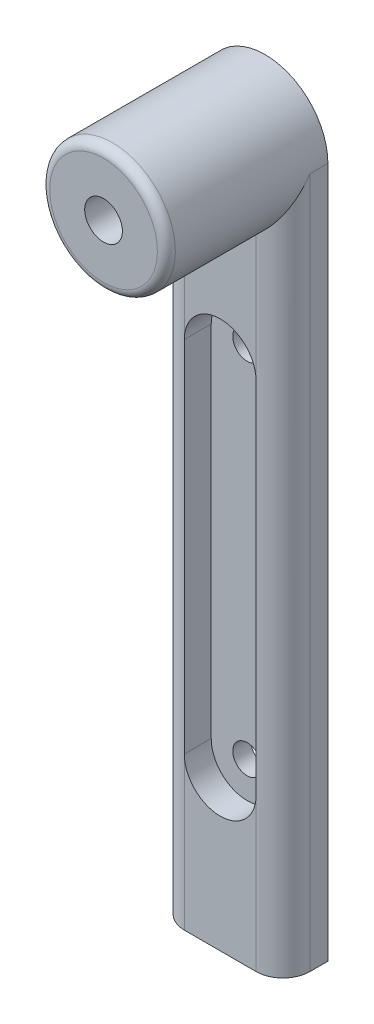
SolidWorks part; units mm, degrees
material "ABS"
ref_plane "Front Plane" through (0, 0, 0) normal (0, 0, 1) x (1, 0, 0)
ref_plane "Top Plane" through (0, 0, 0) normal (0, 1, 0) x (1, 0, 0)
ref_plane "Right Plane" through (0, 0, 0) normal (1, 0, 0) x (0, 0, -1)
sketch "Sketch1" plane through (0, 0, 0) normal (0, 0, 1) x (1, 0, 0)
  circle A0 centre (0, 0) radius 7
  dimension "D1" = 14
extrude "Boss-Extrude1" add sketch "Sketch1" along normal blind 18
sketch "Sketch2" plane through (0, 0, 0) normal (0, 0, 1) x (1, 0, 0)
  line L1 (-7, 0) -> (7, 0)
  line L2 (-7, 0) -> (-7, -77)
  line L3 (-7, -77) -> (7, -77)
  line L4 (7, 0) -> (7, -77)
  dimension "D1" = 77
  dimension "D2" = 0
  dimension "D3" = 14
  dimension "D4" = 7
extrude "Boss-Extrude2" add sketch "Sketch2" along normal blind 5
sketch "Sketch6" plane through (0, 0, 5) normal (0, 0, 1) x (1, 0, 0)
  line L0 (0, -20) -> (0, -60) construction
  line L1 (4, -20) -> (4, -60)
  line L2 (-4, -20) -> (-4, -60)
  arc A0 (4, -20) -> (-4, -20) centre (0, -20) ccw
  arc A1 (-4, -60) -> (4, -60) centre (0, -60) ccw
  point P2 (0, -40)
  dimension "D3" = 4
  dimension "D1" = 40
  dimension "D2" = 40
sketch "Sketch8" plane through (0, 0, 18) normal (0, 0, 1) x (1, 0, 0)
  circle A0 centre (0, 0) radius 2.1
  dimension "D1" = 4.2
extrude "Cut-Extrude5" cut sketch "Sketch8" against normal blind 18
fillet "Fillet3" radius 3 2 edges at (7, -38.5, 5) (-7, -38.5, 5)
extrude "Cut-Extrude6" cut sketch "Sketch6" against normal blind 3
sketch "Sketch10" plane through (0, 0, 2) normal (0, 0, 1) x (1, 0, 0)
  circle A0 centre (0, -20) radius 1.6
  circle A1 centre (0, -60) radius 1.6
  dimension "D1" = 3.2
  dimension "D2" = 3.2
extrude "Cut-Extrude7" cut sketch "Sketch10" against normal blind 3
fillet "Fillet4" radius 1 1 edges at (7, 0, 18)
